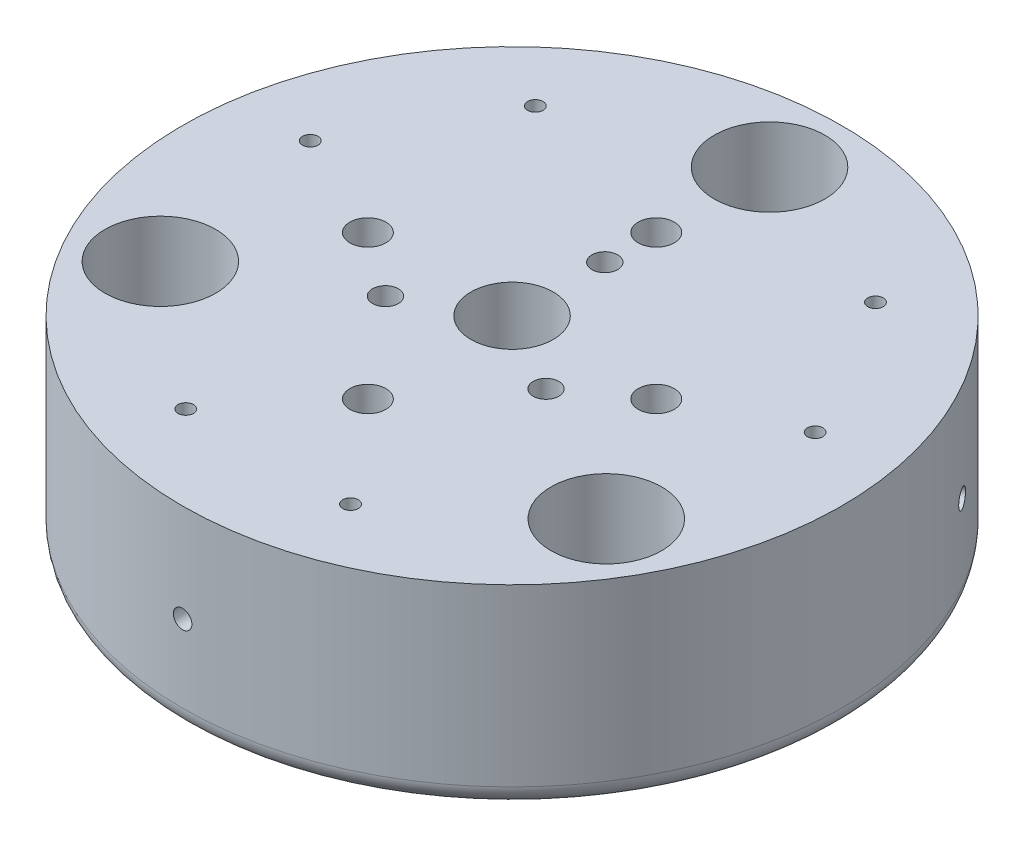
SolidWorks part; units mm, degrees
ref_plane "Спереди" through (0, 0, 0) normal (0, 0, 1) x (1, 0, 0)
ref_plane "Сверху" through (0, 0, 0) normal (0, 1, 0) x (1, 0, 0)
ref_plane "Справа" through (0, 0, 0) normal (1, 0, 0) x (0, 0, -1)
sketch "Эскиз1" plane through (0, 0, 0) normal (0, 1, 0) x (1, 0, 0)
  circle A3 centre (0, 0) radius 32
  circle A4 centre (0, 0) radius 4
  circle A6 centre (0, 0) radius 25 construction
  circle A7 centre (0, 25) radius 3
  circle A8 centre (21.6506, -12.5) radius 3
  circle A9 centre (-21.6506, -12.5) radius 3
  dimension "D4" = 64
  dimension "D1" = 8
  dimension "D2" = 50
  dimension "D3" = 6
  dimension "D5" = 3
extrude "Бобышка-Вытянуть1" add sketch "Эскиз1" along normal blind 19
fillet "Скругление1" radius 2 1 edges at (0, 0, 32)
sketch "Эскиз2" plane through (0, 19, 0) normal (0, 1, 0) x (1, 0, 0)
  circle A0 centre (0, 25) radius 5.375
  circle A2 centre (21.6506, -12.5) radius 5.375
  circle A3 centre (-21.6506, -12.5) radius 5.375
  circle A4 centre (-21.6506, -12.5) radius 3 construction
  dimension "D1" = 10.75
extrude "Вырез-Вытянуть1" cut sketch "Эскиз2" against normal blind 15.5
sketch "Эскиз3" plane through (0, 0, 0) normal (0, -1, 0) x (1, 0, 0)
  circle A0 centre (0, 0) radius 25 construction
  circle A1 centre (0, 25) radius 2.625
  circle A2 centre (21.6506, -12.5) radius 2.625
  circle A3 centre (-21.6506, -12.5) radius 2.625
  dimension "D1" = 5.25
extrude "Вырез-Вытянуть2" cut sketch "Эскиз3" against normal blind 15
sketch "Эскиз4" plane through (0, 0, 0) normal (0, -1, 0) x (1, 0, 0)
  circle A0 centre (0, 0) radius 14 construction
  circle A1 centre (0, 14) radius 1.75
  circle A2 centre (14, 0) radius 1.75
  circle A3 centre (0, -14) radius 1.75
  circle A4 centre (-14, 0) radius 1.75
  dimension "D1" = 28
  dimension "D2" = 3.5
  dimension "D3" = 4
extrude "Вырез-Вытянуть3" cut sketch "Эскиз4" against normal through all
sketch "Эскиз5" plane through (0, 19, 0) normal (0, 1, 0) x (1, 0, 0)
  circle A0 centre (0, 0) radius 9 construction
  circle A1 centre (0, 9) radius 1.25
  circle A2 centre (7.7942, -4.5) radius 1.25
  circle A3 centre (-7.7942, -4.5) radius 1.25
  dimension "D1" = 18
  dimension "D2" = 2.5
  dimension "D3" = 3
extrude "Вырез-Вытянуть4" cut sketch "Эскиз5" against normal through all
sketch "Эскиз6" plane through (0, 0, 0) normal (0, -1, 0) x (1, 0, 0)
  circle A0 centre (0, 14) radius 3
  circle A4 centre (14, 0) radius 3
  circle A5 centre (0, -14) radius 3
  circle A6 centre (-14, 0) radius 3
  circle A7 centre (14, 0) radius 1.75 construction
  dimension "D1" = 6
extrude "Вырез-Вытянуть5" cut sketch "Эскиз6" against normal offset from surface (8 mm away) 11 up to face at (0, 19, -7.75)
sketch "Эскиз7" plane through (0, 0, 0) normal (0, -1, 0) x (1, 0, 0)
  circle A0 centre (7.7942, 4.5) radius 1.95
  circle A1 centre (0, -9) radius 1.95
  circle A2 centre (-7.7942, 4.5) radius 1.95
  circle A3 centre (0, -9) radius 1.25 construction
  dimension "D1" = 3.9
extrude "Вырез-Вытянуть6" cut sketch "Эскиз7" against normal offset from surface (3 mm away) 16 up to face at (0, 19, -7.75)
chamfer "Фаска1" distance 1 angle 45 7 edges at (0, 0, 22.375) (0, 0, -22) (21.6506, 0, -15.125) (21.6506, 0, 15.5) (-21.6506, 0, 15.5) (-21.6506, 0, -15.125) (0, 0, 4)
sketch "Эскиз8" plane through (0, 0, 0) normal (0, -1, 0) x (1, 0, 0)
  line L0 (0, 0) -> (0, 25) construction
  line L1 (-8, 23.6854) -> (8, 23.6854) construction
  circle A0 centre (0, 0) radius 25 construction
  circle A1 centre (-8, 23.6854) radius 0.75
  circle A2 centre (8, 23.6854) radius 0.75
  circle A3 centre (24.5122, -4.9145) radius 0.75
  circle A4 centre (16.5122, -18.7709) radius 0.75
  circle A5 centre (-16.5122, -18.7709) radius 0.75
  circle A6 centre (-24.5122, -4.9145) radius 0.75
  dimension "D1" = 16
  dimension "D2" = 1.5
  dimension "D3" = 1.5
extrude "Вырез-Вытянуть7" cut sketch "Эскиз8" against normal through all
ref_plane "Плоскость1" through (0, 0, 32) normal (0, 0, 1) x (1, 0, 0)
sketch "Эскиз9" plane through (0, 0, 32) normal (0, 0, 1) x (1, 0, 0)
  line L0 (0, 19) -> (0, 0) construction
  line L1 (1.75, 19) -> (-1.75, 19) construction
  line L2 (-30, 0) -> (30, 0) construction
  circle A0 centre (0, 9.5) radius 0.9
  dimension "D1" = 1.8
extrude "Вырез-Вытянуть8" cut sketch "Эскиз9" against normal up to next
pattern_circular "Круговой массив1" count 3 over 360 about axis through (0, 19, 0) along (0, -1, 0) of "Вырез-Вытянуть8" reverse direction yes
equation "\"motor_diameter\"= 30"
equation "\"mm_diameter\"= IIF ( \"motor_diameter\" < 34 , 41 , \"motor_diameter\" + 8 )"
equation "\"upper_shafts_diameter\"= 5"
equation "\"upper_shats_length\"= 180"
equation "\"upper_bearing_d1\"= 10"
equation "\"upper_bearing_d2\"= 5"
equation "\"upper_bearing_h\"= 15"
equation "\"lower_shafts_diameter\"= 5"
equation "\"lower_shafts_length\"= 180"
equation "\"lower_bearing_d1\"= 10"
equation "\"lower_bearing_d2\"= 5"
equation "\"lower_bearing_h\"= 15"
equation "\"print_offset\"= 0.5"
equation "\"bh_screws_d\"= 2"
equation "\"bh_screws_h\"= 20"
equation "\"bh_screws_hh_d\"= 3.4"
equation "\"bh_screws_hh_h\"= 2"
equation "\"bh_nut_d\"= 3.8"
equation "\"bh_nut_h\"= 2"
equation "\"motor_screws_d\"= 3"
equation "\"motor_screws_h\"= 16"
equation "\"motor_screws_hh_d\"= 5.5"
equation "\"motor_screws_hh_h\"= 3"
equation "\"plate_hole_distance\"= 25.4"
equation "\"plate_screws_d\"= 6.5"
equation "\"shafts_diameter\"= IIF ( \"mm_diameter\" < 42 , 42 + 8 , \"mm_diameter\" + 8 )"
equation "\"D4@Эскиз1\"= \"system_radius\" * 2"
equation "\"central_hole_diameter\"= 8"
equation "\"bh_thikness\"= 4"
equation "\"D1@Эскиз1\"=\"central_hole_diameter\""
equation "\"D2@Эскиз1\"=\"shafts_diameter\""
equation "\"D3@Эскиз1\"=\"upper_shafts_diameter\"+1"
equation "\"D1@Бобышка-Вытянуть1\"=\"bh_thikness\"+\"upper_bearing_h\""
equation "\"D1@Эскиз2\"=\"upper_bearing_d1\"+\"print_offset\"*1.5"
equation "\"D1@Вырез-Вытянуть1\"=\"upper_bearing_h\"+\"print_offset\""
equation "\"D1@Эскиз3\"=\"lower_shafts_diameter\"+\"print_offset\"/2"
equation "\"D1@Вырез-Вытянуть2\"=\"lower_bearing_h\""
equation "\"D2@Эскиз4\"=\"motor_screws_d\"+\"print_offset\""
equation "\"D2@Эскиз5\"=\"bh_screws_d\"+\"print_offset\""
equation "\"D1@Эскиз6\"=\"motor_screws_hh_d\"+\"print_offset\""
equation "\"D1@Вырез-Вытянуть5\"=\"motor_screws_h\"-5"
equation "\"D1@Эскиз7\"=\"bh_screws_hh_d\"+\"print_offset\""
equation "\"D1@Вырез-Вытянуть6\"=\"bh_screws_h\"-\"bh_thikness\""
equation "\"D2@Эскиз8\"=\"bh_screws_d\"-\"print_offset\""
equation "\"D3@Эскиз8\"=\"D2@Эскиз8\""
equation "\"ends_screws_d\"= 4"
equation "\"ends_screws_h\"= 16"
equation "\"ends_screws_hh_d\"= 6.7"
equation "\"ends_screws_hh_h\"= 4.1"
equation "\"ends_nut_d\"= 6.8"
equation "\"ends_nut_h\"= 3"
equation "\"system_radius\" = ( \"shafts_diameter\" + 12 + \"bh_thikness\" / 2 ) / 2"
equation "\"encoder_distance\"= \"system_radius\" + 4"
equation "\"tape_position\"= \"encoder_distance\" - 2 + 3.9 + 1.7 / 2"
equation "\"D1@Эскиз9\"=\"bh_screws_d\"-0.2"
